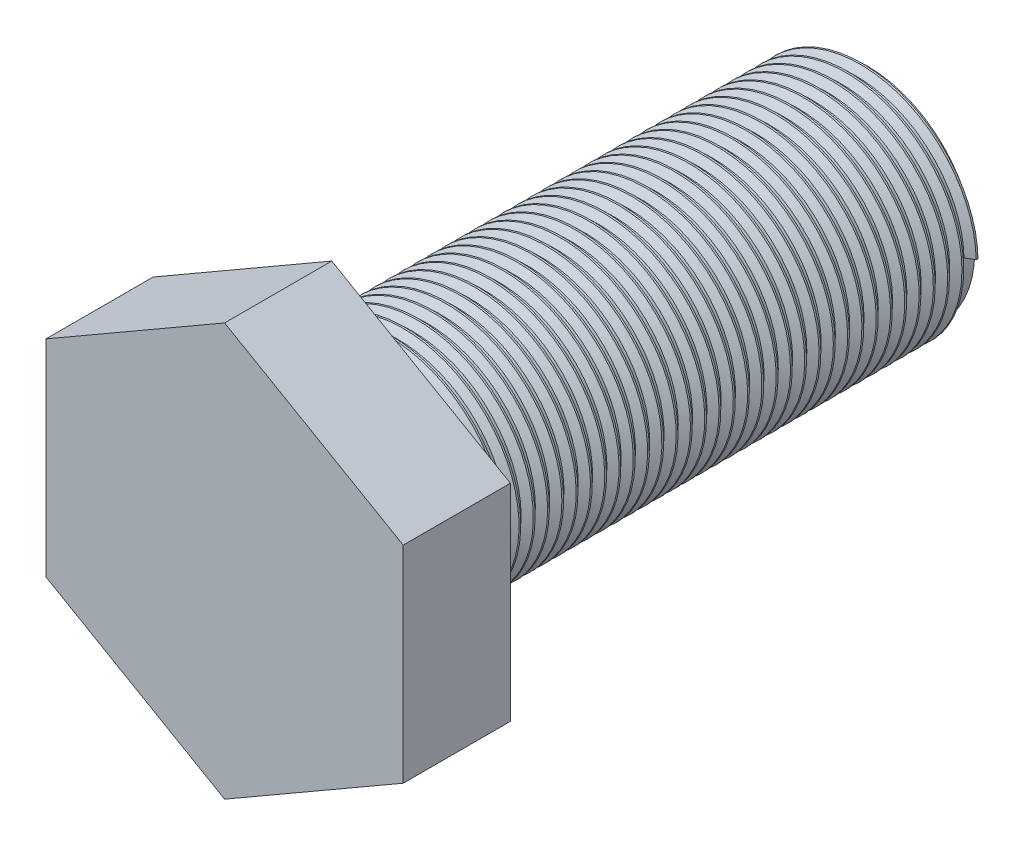
SolidWorks part; units mm, degrees
material "Cobre"
ref_plane "Front" through (0, 0, 0) normal (0, 0, 1) x (1, 0, 0)
ref_plane "Top" through (0, 0, 0) normal (0, 1, 0) x (1, 0, 0)
ref_plane "Right" through (0, 0, 0) normal (1, 0, 0) x (0, 0, -1)
sketch "Croquis1" plane through (0, 0, 0) normal (0, 0, 1) x (1, 0, 0)
  circle A0 centre (0, 0) radius 3
  dimension "D1" = 6
extrude "Saliente-Extruir1" add sketch "Croquis1" along normal blind 15
sketch "Croquis2" plane through (0, 0, 15) normal (0, 0, 1) x (1, 0, 0)
  line L1 (0, 5.7735) -> (-5, 2.8868)
  line L2 (-5, 2.8868) -> (-5, -2.8868)
  line L3 (-5, -2.8868) -> (0, -5.7735)
  line L4 (0, -5.7735) -> (5, -2.8868)
  line L5 (5, -2.8868) -> (5, 2.8868)
  line L6 (5, 2.8868) -> (0, 5.7735)
  circle A0 centre (0, 0) radius 5 construction
  dimension "D1" = 10
extrude "Saliente-Extruir2" add sketch "Croquis2" along normal blind 3
thread "Rosca1" pitch 0.4 method extrude profile "Perfil de rosca1" start angle 0, offset 0, length 15, pitch 0.4, diameter 6
ref_plane "Plano1" through (3, 0, 0) normal (0, -1, 0) x (1, 0, 0)
sketch "Perfil de rosca1" plane through (3, 0, 0) normal (0, -1, 0) x (1, 0, 0)
  line L0 (0, 0) -> (0, 0.4) construction
  line L1 (0, 0) -> (0.2165, 0.125)
  line L2 (0.2165, 0.125) -> (0.2165, 0.175)
  line L3 (0.2165, 0.175) -> (0, 0.3)
  line L4 (0.2165, 0.15) -> (0, 0.15) construction
  line L11 (0, 0) -> (0, 0.3)
  point P2 (0, 0)
  dimension "Pitch" = 0.4
  dimension "Profile_Angle" = 60
  dimension "Profile_Land" = 0.05
  dimension "Profile_Height" = 0.2165
